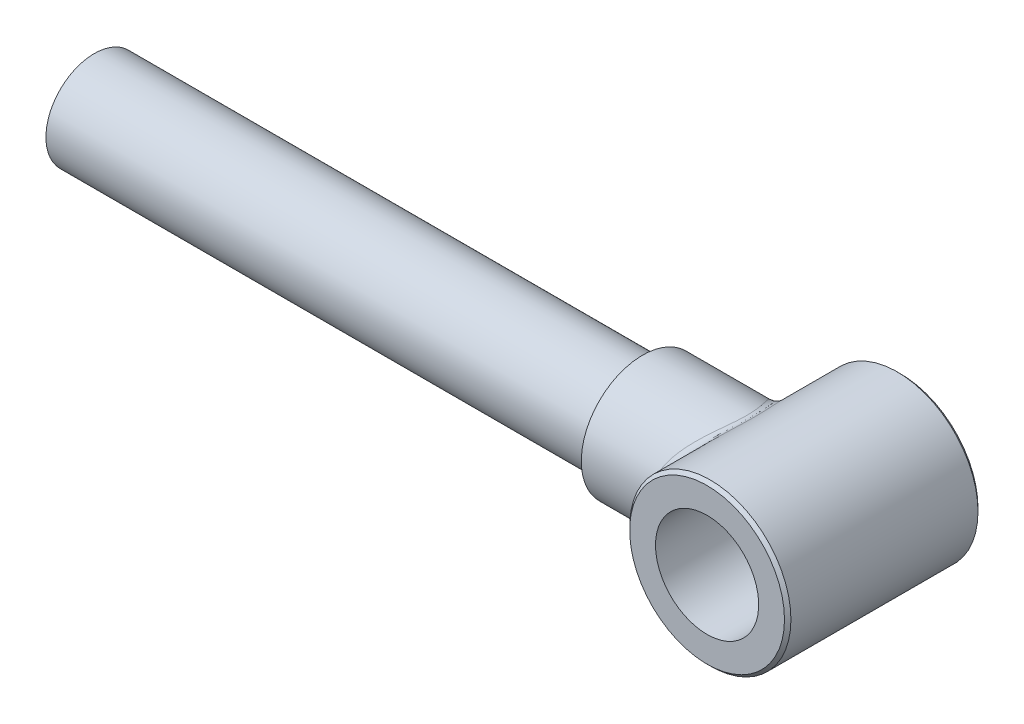
SolidWorks part; units mm, degrees
ref_plane "前视基准面" through (0, 0, 0) normal (0, 0, 1) x (1, 0, 0)
ref_plane "上视基准面" through (0, 0, 0) normal (0, 1, 0) x (1, 0, 0)
ref_plane "右视基准面" through (0, 0, 0) normal (1, 0, 0) x (0, 0, -1)
sketch "草图1" plane through (0, 0, 0) normal (1, 0, 0) x (0, 0, -1)
  circle A0 centre (0, 0) radius 15
  dimension "D1" = 30
extrude "凸台-拉伸1" add sketch "草图1" along normal blind 170
sketch "草图3" plane through (170, 0, 0) normal (1, 0, 0) x (0, 0, -1)
  circle A0 centre (0, 0) radius 19
  dimension "D1" = 38
extrude "凸台-拉伸2" add sketch "草图3" along normal blind 50
sketch "草图4" plane through (0, 0, 0) normal (0, 0, 1) x (1, 0, 0)
  line L0 (220, -19) -> (220, 19) construction
  circle A0 centre (220, 0) radius 25
  dimension "D1" = 50
extrude "凸台-拉伸3" add sketch "草图4" along normal mid plane 60
sketch "草图5" plane through (0, 0, -30) normal (0, 0, -1) x (-1, 0, 0)
  circle A0 centre (-220, 0) radius 16
  circle A1 centre (-220, 0) radius 25 construction
  dimension "D1" = 32
extrude "切除-拉伸1" cut sketch "草图5" against normal through all both and the other way through all
chamfer "倒角1" distance 1 angle 45 2 edges at (245, 0, -30) (245, 0, 30)
fillet "圆角1" radius 4 1 edges at (195.0293, 1.2098, -18.9614)
